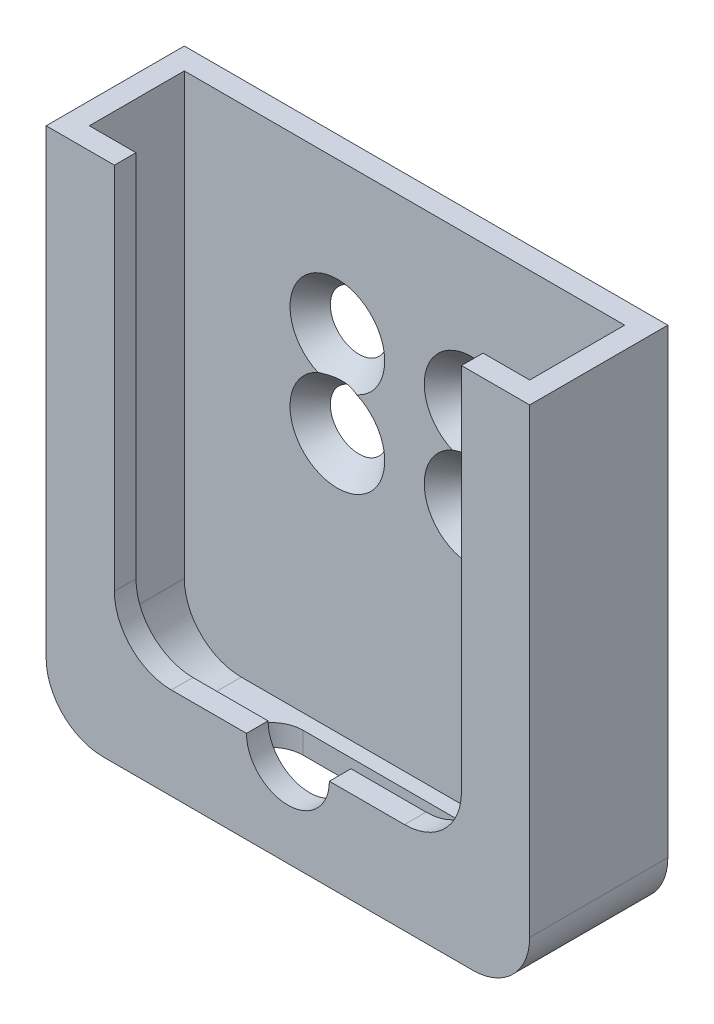
SolidWorks part; units mm, degrees
ref_plane "Front Plane" through (0, 0, 0) normal (0, 0, 1) x (1, 0, 0)
ref_plane "Top Plane" through (0, 0, 0) normal (0, 1, 0) x (1, 0, 0)
ref_plane "Right Plane" through (0, 0, 0) normal (1, 0, 0) x (0, 0, -1)
sketch "Sketch1" plane through (0, 0, 0) normal (0, 0, 1) x (1, 0, 0)
  line L1 (0, 0) -> (71.12, 0)
  line L2 (0, 0) -> (0, 76.2)
  line L3 (0, 76.2) -> (71.12, 76.2)
  line L4 (71.12, 0) -> (71.12, 76.2)
  dimension "D1" = 71.12
  dimension "D2" = 76.2
extrude "Boss-Extrude1" add sketch "Sketch1" along normal mid plane 20.32
sketch "Sketch2" plane through (0, 76.2, 0) normal (0, 1, 0) x (1, 0, 0)
  line L0 (3.175, 6.985) -> (67.945, 6.985)
  line L1 (67.945, 6.985) -> (67.945, -6.985)
  line L2 (3.175, -6.985) -> (67.945, -6.985)
  line L3 (71.12, -10.16) -> (0, -10.16) construction
  line L8 (3.175, -6.985) -> (3.175, 6.985)
  line L9 (71.12, 10.16) -> (0, 10.16) construction
  line L10 (0, -10.16) -> (0, 10.16) construction
  line L11 (71.12, -10.16) -> (71.12, 10.16) construction
  line L12 (35.56, 16.362) -> (35.56, -10.4064) construction
  point P17 (35.56, 6.985)
  dimension "D1" = 3.175
  dimension "D2" = 3.175
  dimension "D3" = 3.175
  dimension "D4" = 3.175
extrude "Cut-Extrude1" cut sketch "Sketch2" against normal offset from surface (73.025 mm away) 3.175 up to face at (35.56, 0, 0)
sketch "Sketch3" plane through (0, 76.2, 0) normal (0, 1, 0) x (1, 0, 0)
  line L0 (71.12, -10.16) -> (0, -10.16) construction
  line L1 (10.033, -10.16) -> (61.087, -10.16)
  line L2 (10.033, -10.16) -> (10.033, -6.985)
  line L3 (10.033, -6.985) -> (61.087, -6.985)
  line L4 (61.087, -10.16) -> (61.087, -6.985)
  line L5 (3.175, -6.985) -> (67.945, -6.985) construction
  line L6 (35.56, 12.6207) -> (35.56, -18.9707) construction
  line L7 (71.12, 10.16) -> (0, 10.16) construction
  point P13 (35.56, 10.16)
  dimension "D1" = 51.054
extrude "Cut-Extrude2" cut sketch "Sketch3" against normal offset from surface (62.6618 mm away) 13.5382 up to face at (35.56, 0, 0)
fillet "Fillet1" radius 8.382 4 edges at (67.945, 3.175, 0) (3.175, 3.175, 0) (10.033, 13.5382, 8.5725) (61.087, 13.5382, 8.5725)
fillet "Fillet2" radius 8.382 2 edges at (0, 0, 0) (71.12, 0, 0)
sketch "Sketch4" plane through (0, 0, 10.16) normal (0, 0, 1) x (1, 0, 0)
  line L0 (52.705, 13.5382) -> (18.415, 13.5382) construction
  circle A0 centre (35.56, 13.5382) radius 6.096
  dimension "D1" = 12.192
extrude "Cut-Extrude3" cut sketch "Sketch4" against normal up to next
hole_wizard "CSK for 1/4 Flat Head Socket Cap Screw1" positions "Sketch8" profile "Sketch9" countersink size "1/4" standard "ANSI Inch" end condition through all
sketch "Sketch8" plane through (0, 0, -6.985) normal (0, 0, 1) x (1, 0, 0)
  line L1 (35.56, 76.2) -> (35.56, 28.3115) construction
  line L3 (67.945, 76.2) -> (3.175, 76.2) construction
  line L4 (11.557, 3.175) -> (59.563, 3.175) construction
  point P0 (25.6871, 53.975)
  point P2 (45.4329, 53.975)
  point P4 (45.4329, 41.275)
  point P6 (25.6871, 41.275)
  point P20 (35.56, 76.2)
  dimension "D1" = 19.7459
  dimension "D2" = 12.7
  dimension "D3" = 38.1
sketch "Sketch9" plane through (25.6871, 53.975, -6.985) normal (1, 0, 0) x (0, -1, 0)
  line L0 (0, 0) -> (0, 3.175)
  line L1 (0, 3.175) -> (3.3782, 3.175)
  line L2 (3.3782, 3.175) -> (3.3782, 4.1256)
  line L3 (3.3782, 4.1256) -> (6.9645, 0)
  line L5 (6.9645, 0) -> (0, 0)
  line L6 (-3.3782, 4.1256) -> (-6.9645, 0) construction
  line L11 (0, -6.35) -> (0, 107.95) construction
  dimension "Thru Hole Dia." = 6.7564
  dimension "Thru Hole Depth" = 3.175
  dimension "Near C'Sink Dia." = 13.929
  dimension "Near C'Sink Angle" = 82
sketch "Sketch10" plane through (0, 0, 0) normal (0, -1, 0) x (1, 0, 0)
  line L1 (22.86, 4.7625) -> (48.26, 4.7625)
  line L3 (22.86, -4.7625) -> (48.26, -4.7625)
  line L4 (62.738, -10.16) -> (62.738, 10.16) construction
  line L5 (8.382, 10.16) -> (62.738, 10.16) construction
  line L6 (35.56, 26.1077) -> (35.56, 1.2906) construction
  arc A0 (22.86, 4.7625) -> (22.86, -4.7625) centre (22.86, 0) ccw
  arc A1 (48.26, -4.7625) -> (48.26, 4.7625) centre (48.26, 0) ccw
  point P9 (35.56, 10.16)
  point P12 (62.738, 0)
  dimension "D1" = 25.4
  dimension "D2" = 9.525
extrude "Cut-Extrude4" cut sketch "Sketch10" against normal up to next
equation "\"width\"= 2.53in'Phone width"
equation "\"D1@Sketch1\" = \"width\" + 2 * \"wall\" +2*\"margin\"'Overall width of holster"
equation "\"wall\"= 0.125in'Metal thickness"
equation "\"height\"= 3in'Overall holster height"
equation "\"D2@Sketch1\"= \"height\"'Overall holster height"
equation "\"depth\"= 0.53in'Thickness of phone"
equation "\"D1@Boss-Extrude1\"= \"depth\" + 2 * \"wall\" + 2*\"margin\" 'Overal depth of holster"
equation "\"D3@Sketch2\"=\"wall\""
equation "\"D4@Sketch2\"= \"wall\""
equation "\"screen_width\"= 2.01in'Width of visible screen"
equation "\"margin\"= 0.01in'Slop to allow the phone to fit properly"
equation "\"D2@Sketch2\" = \"wall\""
equation "\"D1@Sketch2\"=\"wall\""
equation "\"D1@Cut-Extrude1\"=\"wall\""
equation "\"D1@Sketch3\"=\"screen_width\""
equation "\"D1@Cut-Extrude2\" = \"lower_edge\" + \"wall\""
equation "\"lower_edge\"= .408'How deep the phone sits in the holster"
equation "\"tool_diam\"= .66'Diameter of the tool used for undercuts, set to match the corners of the phone"
equation "\"D1@Fillet1\"=\"tool_diam\"/2"
equation "\"D1@Fillet2\"=\"tool_diam\"/2"
equation "\"button_cutout\"= .48in'Cutout for the iPhone button"
equation "\"D1@Sketch4\" = \"button_cutout\""
